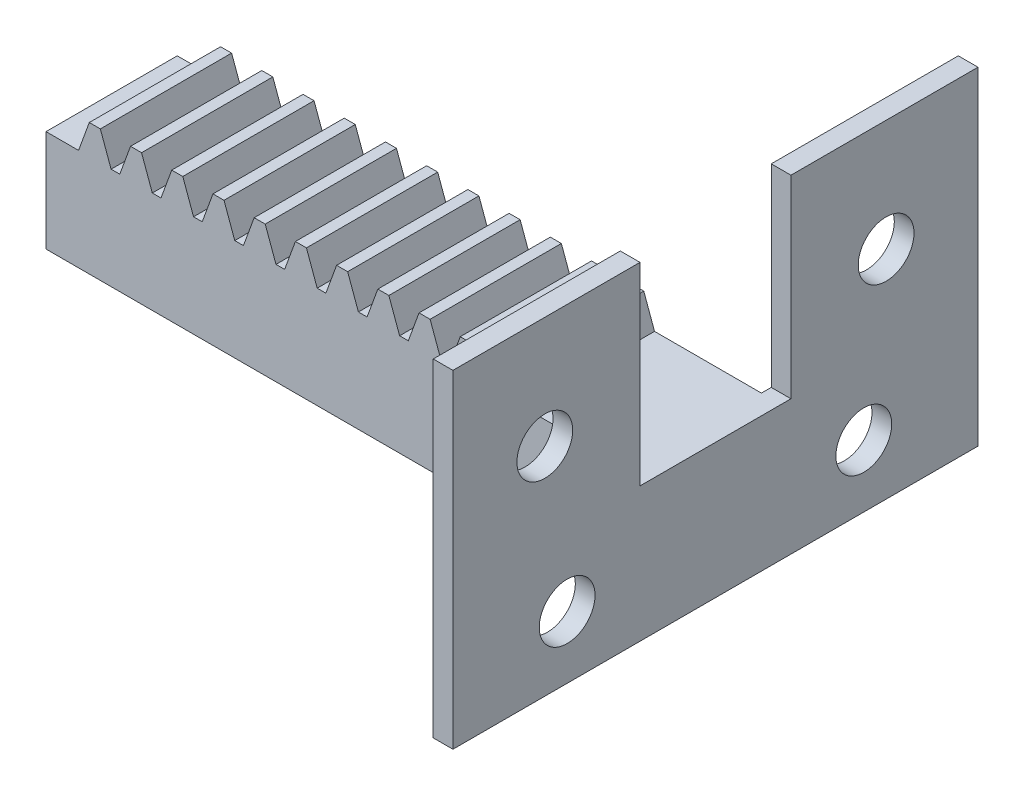
SolidWorks part; units mm, degrees
ref_plane "前视基准面" through (0, 0, 0) normal (0, 0, 1) x (1, 0, 0)
ref_plane "上视基准面" through (0, 0, 0) normal (0, 1, 0) x (1, 0, 0)
ref_plane "右视基准面" through (0, 0, 0) normal (1, 0, 0) x (0, 0, -1)
sketch "草图1" plane through (0, 0, 0) normal (0, 0, 1) x (1, 0, 0)
  line L1 (0, 0) -> (92, 0)
  line L2 (0, 0) -> (0, 20)
  line L3 (0, 20) -> (92, 20)
  line L4 (92, 0) -> (92, 20)
  dimension "H0" = 20
  dimension "L" = 92
extrude "凸台-拉伸1" add sketch "草图1" along normal blind 20
sketch "草图2" plane through (0, 0, 20) normal (0, 0, 1) x (1, 0, 0)
  line L0 (2, 20) -> (3.6379, 15.5)
  line L1 (92, 20) -> (0, 20) construction
  line L2 (3.6379, 15.5) -> (4.9596, 15.5)
  line L3 (4.9596, 15.5) -> (6.5975, 20)
  line L4 (6.5975, 20) -> (2, 20)
  line L5 (0, 18) -> (92, 18) construction
  line L6 (0, 20) -> (0, 0) construction
  line L7 (92, 0) -> (92, 20) construction
  line L9 (8.28, 20) -> (9.9179, 15.5) construction
  line L10 (9.9179, 15.5) -> (4.9596, 15.5) construction
  line L12 (8.28, 20) -> (6.5975, 20) construction
  point P12 (2.7279, 18)
  point P13 (5.8695, 18)
  point P14 (9.0079, 18)
  dimension "H" = 4.5
  dimension "H1" = 2
  dimension "A" = 2
  dimension "P" = 6.28
  dimension "E" = 3.1416
  dimension "D1" = 20
extrude "切除-拉伸1" cut sketch "草图2" against normal through all
pattern_linear "阵列(线性)1" count 14 spacing 6.28 along (1, 0, 0) of "切除-拉伸1"
sketch "草图3" plane through (0, 0, 20) normal (0, 0, 1) x (1, 0, 0)
  line L0 (2, 20) -> (0, 20)
  line L1 (0, 20) -> (0, 15.5)
  line L2 (0, 20) -> (0, 0) construction
  line L3 (0, 15.5) -> (3.6379, 15.5)
  line L4 (3.6379, 15.5) -> (2, 20)
  line L5 (74.0396, 15.5) -> (75.6775, 20)
  line L6 (75.6775, 20) -> (92, 20)
  line L7 (92, 20) -> (92, 15.5)
  line L8 (92, 0) -> (92, 20) construction
  line L9 (92, 15.5) -> (74.0396, 15.5)
extrude "切除-拉伸2" cut sketch "草图3" against normal through all
sketch "草图4" plane through (92, 0, 0) normal (1, 0, 0) x (0, 0, -1)
  line L1 (0, 15.5) -> (0, 45)
  line L3 (-20, 45) -> (-20, 15.5)
  line L4 (-20, 0) -> (-50, 0)
  line L5 (-50, 0) -> (-50, 45)
  line L6 (-50, 45) -> (-20, 45)
  line L7 (-20, 0) -> (-20, 15.5)
  line L8 (0, 45) -> (30, 45)
  line L9 (0, 0) -> (30, 0)
  line L10 (30, 0) -> (30, 45)
  line L11 (0, 0) -> (0, 15.5)
  dimension "D1" = 45
  dimension "D2" = 30
  dimension "D3" = 30
  dimension "D4" = 45
extrude "凸台-拉伸2" add sketch "草图4" against normal blind 3
sketch "草图5" plane through (92, 0, 0) normal (1, 0, 0) x (0, 0, -1)
  line L0 (-21.5, 45) -> (-21.5, 15.5)
  line L1 (-20, 45) -> (-50, 45) construction
  line L2 (-21.5, 15.5) -> (-20, 15.5)
  line L3 (-20, 15.5) -> (-20, 45)
  line L4 (-20, 45) -> (-21.5, 45)
  line L5 (0, 45) -> (0, 15.5)
  line L6 (0, 15.5) -> (1.5, 15.5)
  line L7 (1.5, 15.5) -> (1.5, 45)
  line L8 (30, 45) -> (0, 45) construction
  line L9 (1.5, 45) -> (0, 45)
  dimension "D1" = 1.5
  dimension "D2" = 1.5
extrude "切除-拉伸3" cut sketch "草图5" against normal blind 12
sketch "草图6" plane through (0, 0, 0) normal (0, -1, 0) x (1, 0, 0)
  line L0 (89, 0) -> (89, 20)
  line L8 (0, 0) -> (89, 0)
  line L9 (89, 0) -> (89, -30)
  line L10 (89, -30) -> (92, -30)
  line L11 (92, -30) -> (92, 50)
  line L12 (92, 50) -> (89, 50)
  line L13 (89, 50) -> (89, 20)
  line L14 (89, 20) -> (0, 20)
  line L15 (0, 20) -> (0, 0)
  line L17 (89, 0) -> (89, -30)
  line L18 (89, -30) -> (92, -30)
  line L19 (92, -30) -> (92, 50)
  line L20 (92, 50) -> (89, 50)
  line L21 (89, 50) -> (89, 20)
  dimension "D1" = 0
extrude "凸台-拉伸3" add sketch "草图6" along normal blind 5
sketch "草图7" plane through (92, 0, 0) normal (1, 0, 0) x (0, 0, -1)
  line L0 (30, -5) -> (-50, -5) construction
  line L1 (-50, 45) -> (-50, -5) construction
  line L2 (-10, -5) -> (-10, 15.5) construction
  line L3 (1.5, 15.5) -> (-21.5, 15.5) construction
  circle A0 centre (-36, 28) radius 4.25
  circle A1 centre (16, 28) radius 4.25
  dimension "D1" = 33
  dimension "D3" = 8.5
  dimension "D2" = 14
extrude "切除-拉伸4" cut sketch "草图7" against normal up to surface (3 mm away) up to face at (89, 19.3333, 10)
sketch "草图8" plane through (0, 0, 0) normal (0, -1, 0) x (1, 0, 0)
  line L0 (0, 10) -> (92, 10) construction
  line L1 (0, 20) -> (0, 0) construction
  line L2 (92, -30) -> (92, 50) construction
  circle A0 centre (7.5, 10) radius 1.75
  circle A1 centre (27.5, 10) radius 1.75
  circle A2 centre (47.5, 10) radius 1.75
  dimension "D2" = 20
  dimension "D3" = 20
  dimension "D4" = 3.5
  dimension "D1" = 7.5
extrude "切除-拉伸5" cut sketch "草图8" against normal blind 8
sketch "草图9" plane through (92, 0, 0) normal (1, 0, 0) x (0, 0, -1)
  line L0 (-50, 4.5) -> (30, 4.5) construction
  line L1 (-50, 45) -> (-50, -5) construction
  line L2 (30, -5) -> (30, 45) construction
  line L3 (30, -5) -> (-50, -5) construction
  line L4 (-10, -5) -> (-10, 15.5) construction
  line L5 (1.5, 15.5) -> (-21.5, 15.5) construction
  circle A0 centre (-32.6, 4.5) radius 4.25
  circle A1 centre (12.6, 4.5) radius 4.25
  dimension "D2" = 8.5
  dimension "D3" = 45.2
  dimension "D1" = 9.5
extrude "切除-拉伸6" cut sketch "草图9" against normal through all
equation "\"D3@阵列(线性)1\"= \"P@草图2\""
